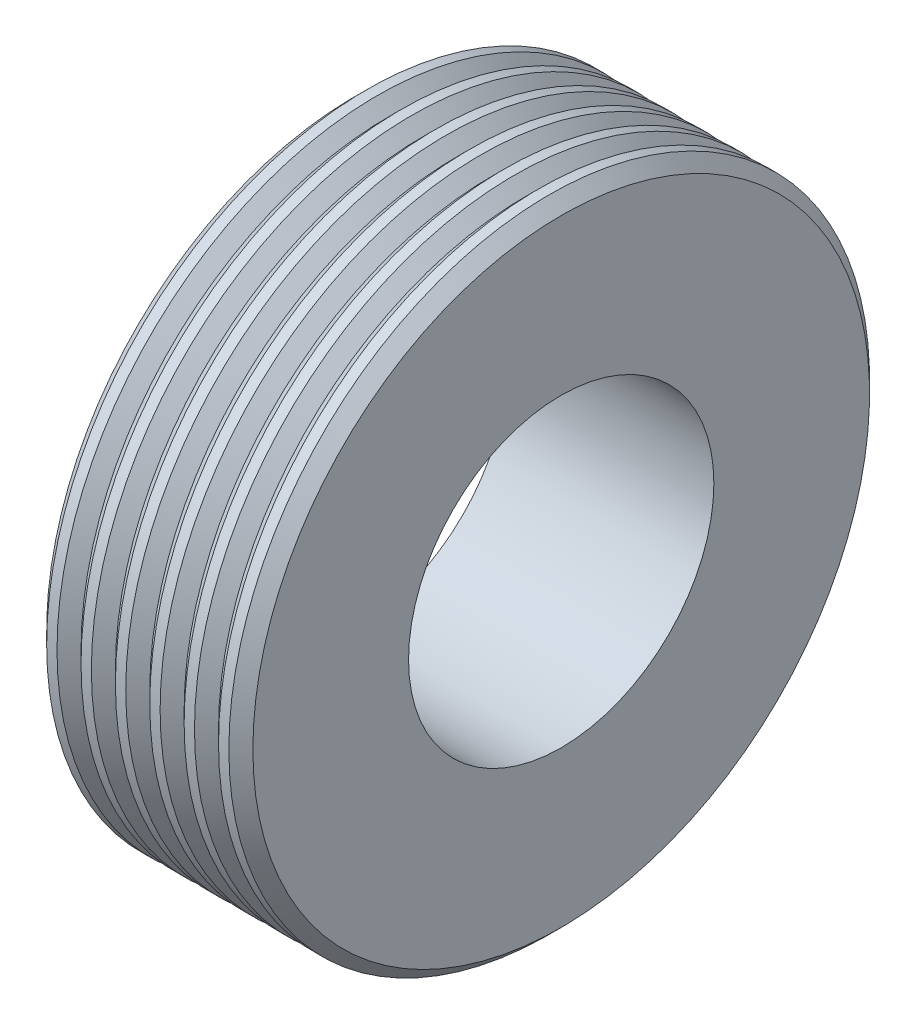
SolidWorks part; units mm, degrees
material "3D Printed PLA"
ref_plane "Front Plane" through (0, 0, 0) normal (0, 0, 1) x (1, 0, 0)
ref_plane "Top Plane" through (0, 0, 0) normal (0, 1, 0) x (1, 0, 0)
ref_plane "Right Plane" through (0, 0, 0) normal (1, 0, 0) x (0, 0, -1)
ref_axis "Axis1" through (0, 55, 0) along (0, -1, 0)
ref_axis "Axis2" through (-88.99, 0, 0) along (1, 0, 0)
ref_axis "Axis3" through (0, 0, -88.99) along (0, 0, 1)
sketch "Sketch1" plane through (0, 0, 0) normal (0, 0, 1) x (1, 0, 0)
  line L0 (-5.25, 16) -> (5.25, 16) construction
  line L1 (-5.15, 16) -> (5.15, 16)
  line L2 (-5.15, 16) -> (-5.15, 7.6246)
  line L3 (-5.15, 7.6246) -> (5.15, 7.6246)
  line L4 (5.15, 16) -> (5.15, 7.6246)
  line L5 (-5.15, 16) -> (-5.25, 16) construction
  line L6 (0, 0) -> (50000, 0) construction
  line L7 (0, 0) -> (0, 50000) construction
  line L8 (-5.25, 16) -> (-5.25, -16) construction
  line L9 (5.15, 7.5246) -> (5.15, 7.6246) construction
  line L10 (-5.05, 7.5246) -> (5.25, 7.5246) construction
  dimension "D1" = 0.1
revolve "Revolve1" add sketch "Sketch1" angle 360 about L6
chamfer "Chamfer1" distance 0.6 angle 45 2 edges at (5.15, 0, 16) (-5.15, 0, 16)
sketch "Sketch2" plane through (0, 0, 0) normal (0, 0, 1) x (1, 0, 0)
  line L0 (-4.0333, 16) -> (-3.4333, 15.4)
  line L1 (-5.15, 16) -> (5.15, 16) construction
  line L2 (-3.4333, 15.4) -> (-2.8333, 16)
  line L3 (-2.8333, 16) -> (-4.0333, 16)
  line L4 (-3.4333, 15.4) -> (-3.4333, 16) construction
  line L5 (-5.15, 15.4) -> (-3.4333, 15.4) construction
  line L6 (-1.7167, 15.4) -> (-1.1167, 16)
  line L7 (-1.1167, 16) -> (-2.3167, 16)
  line L8 (-2.3167, 16) -> (-1.7167, 15.4)
  line L9 (0, 15.4) -> (0.6, 16)
  line L10 (0.6, 16) -> (-0.6, 16)
  line L11 (-0.6, 16) -> (0, 15.4)
  line L12 (1.7167, 15.4) -> (2.3167, 16)
  line L13 (2.3167, 16) -> (1.1167, 16)
  line L14 (1.1167, 16) -> (1.7167, 15.4)
  line L15 (3.4333, 15.4) -> (4.0333, 16)
  line L16 (4.0333, 16) -> (2.8333, 16)
  line L17 (2.8333, 16) -> (3.4333, 15.4)
  line L18 (5.15, 15.4) -> (3.4333, 15.4) construction
  line L19 (-4.55, 16) -> (-4.0333, 16) construction
  line L20 (-2.8333, 16) -> (-2.3167, 16) construction
  dimension "D1" = 0.5167
  dimension "D2" = 5
revolve "Cut-Revolve1" cut sketch "Sketch2" angle 360 about L6
